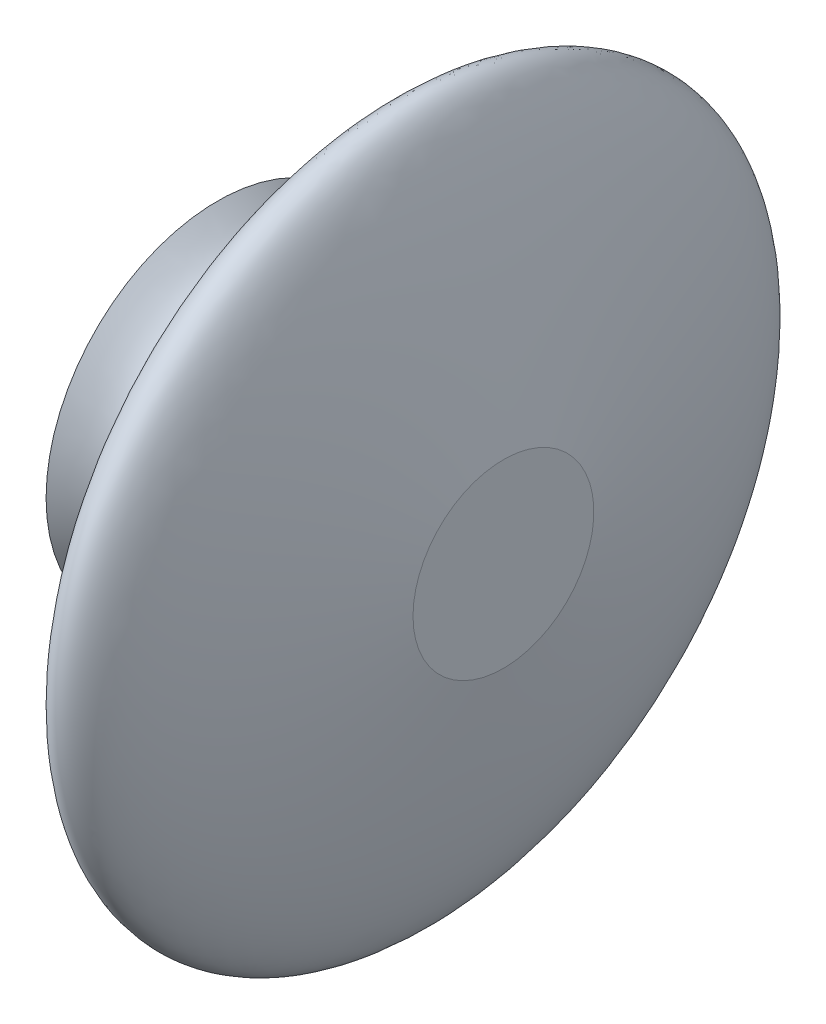
SolidWorks part; units mm, degrees
ref_plane "Front Plane" through (0, 0, 0) normal (0, 0, 1) x (1, 0, 0)
ref_plane "Top Plane" through (0, 0, 0) normal (0, 1, 0) x (1, 0, 0)
ref_plane "Right Plane" through (0, 0, 0) normal (1, 0, 0) x (0, 0, -1)
sketch "Sketch1" plane through (0, 0, 0) normal (0, 1, 0) x (1, 0, 0)
  line L0 (0, 76.2) -> (0, 0)
  line L1 (0, 0) -> (127, 0)
  line L2 (127, 0) -> (127, 40.1749)
  spline S0 degree 4 poles (-12.6998, 87.3453) (-12.4772, 87.2031) (-12.0347, 86.9137) (-11.1598, 86.3131) (-9.8912, 85.3706) (-8.4394, 84.1976) (-7.058, 83.0004) (-5.8552, 81.9046) (-4.7513, 80.8752) (-3.4789, 79.6498) (-2.4153, 78.6114) (-0.473, 76.6743) (0.4928, 75.7058) (2.2466, 73.9568) (3.1881, 73.0351) (4.2434, 72.0123) (4.9968, 71.297) (5.7917, 70.5546) (6.5876, 69.8287) (7.5953, 68.9335) (9.2372, 67.5349) (11.3676, 65.8761) (14.088, 64.1003) (17.053, 62.7339) (19.7009, 62.0321) (22.5472, 61.8421) (25.1919, 62.2683) (27.7355, 63.3008) (30.5226, 65.0655) (33.157, 67.3578) (35.8606, 70.377) (38.5917, 74.0989) (41.1032, 78.0557) (43.4558, 82.1931) (45.7294, 86.5439) (47.9486, 91.0907) (50.1346, 95.8196) (52.3072, 100.7197) (54.4268, 105.6427) (56.5137, 110.5797) (58.5865, 115.5226) (60.6631, 120.4639) (62.7626, 125.3956) (64.9062, 130.3083) (66.8433, 134.5798) (68.569, 138.2108) (70.0654, 141.2082) (71.3055, 143.584) (72.9186, 146.5167) (74.639, 149.3856) (76.5037, 152.1644) (78.5262, 154.6956) (80.2218, 156.49) (82.1097, 158.0709) (84.1002, 159.2355) (86.0845, 159.7867) (87.8593, 159.7363) (89.7733, 159.2523) (91.4828, 158.2958) (93.0877, 156.9247) (94.9195, 154.8739) (96.7317, 152.3505) (98.6726, 149.0132) (100.6794, 144.861) (102.5674, 140.3457) (104.3754, 135.5034) (106.1204, 130.3483) (107.8176, 124.8871) (109.4786, 119.131) (111.4388, 111.8991) (113.6385, 103.1878) (116.0437, 92.9743) (118.6312, 81.2805) (121.1078, 69.5492) (123.2082, 59.2535) (124.94, 50.6008) (126.9851, 40.264) (128.1708, 34.2149) (130.8452, 20.5825) (131.3994, 17.7643) (132.421, 12.5915) knots 0 0 0 0 0 0.003282 0.006565 0.01313 0.019694 0.026259 0.029542 0.032824 0.039389 0.045954 0.052518 0.059209 0.065899 0.069244 0.072589 0.075934 0.079279 0.082624 0.085969 0.092659 0.106039 0.116107 0.126175 0.132999 0.139822 0.151319 0.159054 0.166789 0.180638 0.194486 0.209245 0.224005 0.238765 0.253524 0.270151 0.286779 0.303406 0.320033 0.33666 0.353287 0.369914 0.386541 0.403168 0.419796 0.428109 0.436423 0.444736 0.45305 0.469632 0.477924 0.486215 0.493217 0.500219 0.50839 0.514639 0.518323 0.522008 0.532762 0.538589 0.544416 0.55607 0.571247 0.586425 0.601602 0.61678 0.635368 0.653956 0.672545 0.691133 0.72831 0.765486 0.802663 0.83984 0.877016 0.895605 0.914193 0.957097 1 1 1 1 1 construction
  spline S1 degree 4 poles (0, 76.2) (0.3285, 75.8715) (0.9872, 75.2128) (2.2466, 73.9568) (3.1881, 73.0351) (4.2434, 72.0123) (4.9968, 71.297) (5.7917, 70.5546) (6.5876, 69.8287) (7.5953, 68.9335) (9.2372, 67.5349) (11.3676, 65.8761) (14.088, 64.1003) (17.053, 62.7339) (19.7009, 62.0321) (22.5472, 61.8421) (25.1919, 62.2683) (27.7355, 63.3008) (30.5226, 65.0655) (33.157, 67.3578) (35.8606, 70.377) (38.5917, 74.0989) (41.1032, 78.0557) (43.4558, 82.1931) (45.7294, 86.5439) (47.9486, 91.0907) (50.1346, 95.8196) (52.3072, 100.7197) (54.4268, 105.6427) (56.5137, 110.5797) (58.5865, 115.5226) (60.6631, 120.4639) (62.7626, 125.3956) (64.9062, 130.3083) (66.8433, 134.5798) (68.569, 138.2108) (70.0654, 141.2082) (71.3055, 143.584) (72.9186, 146.5167) (74.639, 149.3856) (76.5037, 152.1644) (78.5262, 154.6956) (80.2218, 156.49) (82.1097, 158.0709) (84.1002, 159.2355) (86.0845, 159.7867) (87.8593, 159.7363) (89.7733, 159.2523) (91.4828, 158.2958) (93.0877, 156.9247) (94.9195, 154.8739) (96.7317, 152.3505) (98.6726, 149.0132) (100.6794, 144.861) (102.5674, 140.3457) (104.3754, 135.5034) (106.1204, 130.3483) (107.8176, 124.8871) (109.4786, 119.131) (111.4388, 111.8991) (113.6385, 103.1878) (116.0437, 92.9743) (118.6312, 81.2805) (121.1078, 69.5492) (123.2082, 59.2535) (124.94, 50.6008) (126.2368, 44.0461) (126.7506, 41.4414) (127, 40.1749) knots 0.052518 0.052518 0.052518 0.052518 0.052518 0.059209 0.065899 0.069244 0.072589 0.075934 0.079279 0.082624 0.085969 0.092659 0.106039 0.116107 0.126175 0.132999 0.139822 0.151319 0.159054 0.166789 0.180638 0.194486 0.209245 0.224005 0.238765 0.253524 0.270151 0.286779 0.303406 0.320033 0.33666 0.353287 0.369914 0.386541 0.403168 0.419796 0.428109 0.436423 0.444736 0.45305 0.469632 0.477924 0.486215 0.493217 0.500219 0.50839 0.514639 0.518323 0.522008 0.532762 0.538589 0.544416 0.55607 0.571247 0.586425 0.601602 0.61678 0.635368 0.653956 0.672545 0.691133 0.72831 0.765486 0.802663 0.83984 0.877016 0.895605 0.914193 0.914193 0.914193 0.914193 0.914193
revolve "Revolve1" add sketch "Sketch1" angle 360 about L1
shell "Shell2" thickness 6.35 removed face at (0, 0, 76.2)
